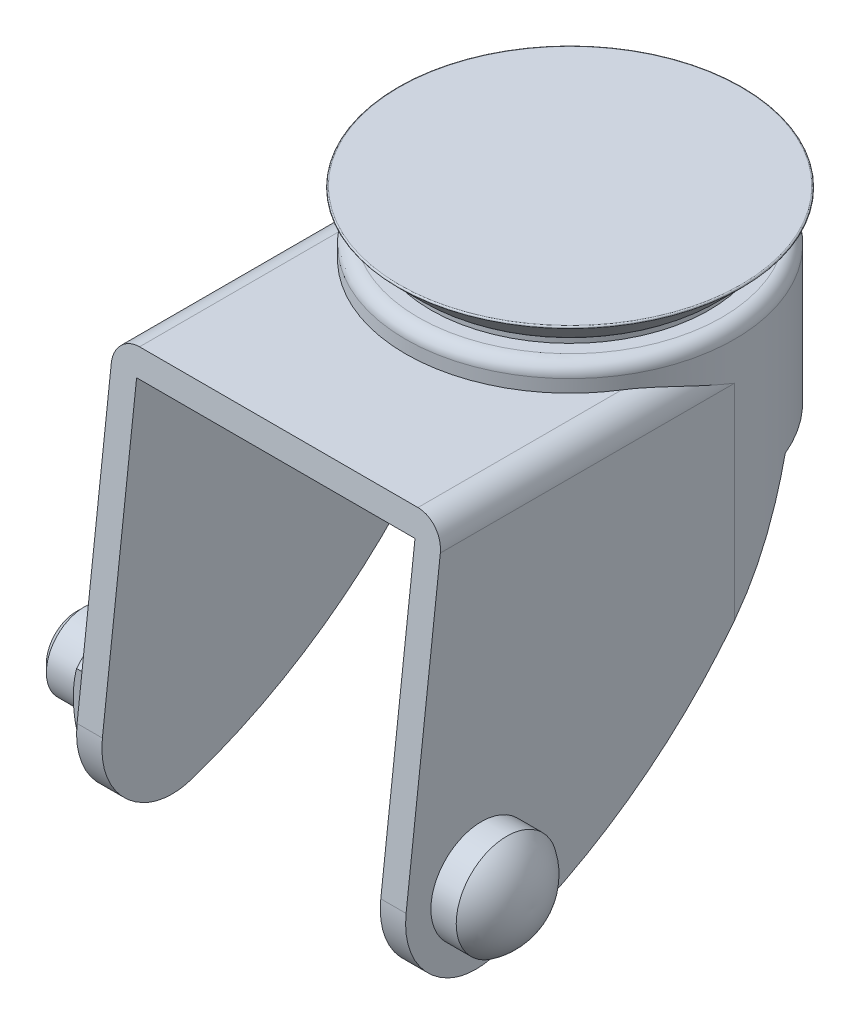
SolidWorks part; units mm, degrees
material "A6061"
ref_plane "前视基准面" through (0, 0, 0) normal (0, 0, 1) x (1, 0, 0)
ref_plane "上视基准面" through (0, 0, 0) normal (0, 1, 0) x (1, 0, 0)
ref_plane "右视基准面" through (0, 0, 0) normal (1, 0, 0) x (0, 0, -1)
sketch "草图1" plane through (0, 0, 0) normal (0, 0, 1) x (1, 0, 0)
  line L0 (0, 0) -> (11, 0)
  line L1 (11, 0) -> (11, -3)
  line L2 (11, -3) -> (12, -3)
  line L3 (13, -4) -> (13, -51)
  line L4 (13, -51) -> (0, -51)
  line L5 (0, -51) -> (0, 0)
  line L6 (0, -51) -> (0, 0) construction
  arc A0 (12, -3) -> (13, -4) centre (12, -4) cw
revolve "旋转1" add sketch "草图1" angle 360 about L6 reverse direction yes
ref_plane "基准面1" through (0, 0, 0) normal (0, 0, 1) x (1, 0, 0)
ref_plane "基准面2" through (0, 0, 0) normal (0, 0, 1) x (1, 0, 0)
sketch "草图2" plane through (0, 0, 0) normal (0, 0, 1) x (1, 0, 0)
  line L0 (-13, -7) -> (-13, -56)
  line L1 (-13, -56) -> (13, -56)
  line L2 (13, -56) -> (13, -7)
  line L3 (11, -5) -> (-11, -5)
  arc A0 (13, -7) -> (11, -5) centre (11, -7) ccw
  arc A1 (-11, -5) -> (-13, -7) centre (-11, -7) ccw
extrude "凸台-拉伸1" add sketch "草图2" along normal blind 60
sketch "草图3" plane through (0, 0, 0) normal (0, 0, 1) x (1, 0, 0)
  line L0 (-11, -58) -> (11, -58)
  line L1 (11, -58) -> (11, -7)
  line L2 (11, -7) -> (-11, -7)
  line L3 (-11, -7) -> (-11, -58)
extrude "切除-拉伸1" cut sketch "草图3" along normal blind 70
ref_plane "基准面3" through (0, -4, 0) normal (0, 1, 0) x (1, 0, 0)
sketch "草图4" plane through (0, -4, 0) normal (0, 1, 0) x (1, 0, 0)
  circle A0 centre (0, 0) radius 11
extrude "切除-拉伸2" cut sketch "草图4" against normal blind 51
sketch "草图5" plane through (0, 0, 0) normal (1, 0, 0) x (0, 0, -1)
  line L0 (-150, -300) -> (150, -300)
  line L1 (150, -300) -> (150, -14.8)
  line L2 (150, -14.8) -> (5, -14.8)
  line L3 (-25.96, -30.3084) -> (-23, -4.8)
  line L4 (-23, -4.8) -> (-150, -4.8)
  line L5 (-150, -4.8) -> (-150, -300)
  arc A0 (5, -14.8) -> (-18.8511, -36.6319) centre (-31.629, 1.2723) cw
  arc A1 (-18.8511, -36.6319) -> (-22.69, -36.3632) centre (-20.4483, -31.8939) cw
  arc A2 (-22.69, -36.3632) -> (-25.96, -30.3084) centre (-20, -31) cw
extrude "切除-拉伸3" cut sketch "草图5" along normal blind 200 and the other way blind 200
ref_plane "基准面4" through (0, 0, 20) normal (0, 0, 1) x (1, 0, 0)
sketch "草图6" plane through (0, 0, 20) normal (0, 0, 1) x (1, 0, 0)
  line L0 (13, -31) -> (13, -27)
  line L1 (13, -27) -> (15, -27)
  line L2 (17, -31) -> (13, -31)
  line L3 (17, -31) -> (13, -31) construction
  arc A0 (15, -27) -> (17, -31) centre (12.5072, -30.7464) cw
revolve "旋转2" add sketch "草图6" angle 360 about L3 reverse direction yes
sketch "草图7" plane through (0, 0, 20) normal (0, 0, 1) x (1, 0, 0)
  line L0 (-19, -31) -> (-19, -28.6135)
  line L1 (-19, -28.6135) -> (-18.3865, -28)
  line L2 (-18.3865, -28) -> (-16, -28)
  line L3 (-16, -28) -> (-16, -28.6)
  line L4 (-15, -26.2) -> (-13, -26.2)
  line L5 (-13, -26.2) -> (-13, -31)
  line L6 (-13, -31) -> (-19, -31)
  line L7 (-13, -31) -> (-19, -31) construction
  arc A0 (-16, -28.6) -> (-15, -26.2) centre (-10.0931, -29.6529) cw
revolve "旋转3" add sketch "草图7" angle 360 about L7 reverse direction yes
cosmetic thread "装饰螺纹线1" parameters "D1"=1.9, "D2"=4.773
ref_plane "基准面5" through (-13, 0, 0) normal (1, 0, 0) x (0, 0, -1)
sketch "草图8" plane through (-13, 0, 0) normal (1, 0, 0) x (0, 0, -1)
  line L0 (-23.6, -33.0785) -> (-20, -35.1569)
  line L1 (-20, -35.1569) -> (-16.4, -33.0785)
  line L2 (-16.4, -33.0785) -> (-16.4, -28.9215)
  line L3 (-16.4, -28.9215) -> (-20, -26.8431)
  line L4 (-20, -26.8431) -> (-23.6, -28.9215)
  line L5 (-23.6, -28.9215) -> (-23.6, -33.0785)
  circle A0 centre (-20, -31) radius 5.3
extrude "切除-拉伸4" cut sketch "草图8" against normal blind 200
sketch "草图9" plane through (0, 0, 0) normal (0, 0, 1) x (1, 0, 0)
  line L0 (0, 0) -> (13.5086, 0)
  line L1 (13.5793, -0.1707) -> (11.5429, -2.2071)
  line L2 (10.8358, -2.5) -> (0, -2.5)
  line L3 (0, -2.5) -> (0, 0)
  line L4 (0, -2.5) -> (0, 0) construction
  arc A0 (13.5086, 0) -> (13.5793, -0.1707) centre (13.5086, -0.1) cw
  arc A1 (11.5429, -2.2071) -> (10.8358, -2.5) centre (10.8358, -1.5) cw
revolve "旋转4" add sketch "草图9" angle 360 about L4 reverse direction yes
ref_plane "body_to_plate XY" through (0, 0, 0) normal (0, 1, 0) x (1, 0, 0)
ref_plane "body_to_plate XZ" through (0, 0, 0) normal (0, 0, 1) x (1, 0, 0)
ref_plane "body_to_plate YZ" through (0, 0, 0) normal (1, 0, 0) x (0, 0, -1)
ref_axis "body_to_plate X" through (-80.9, 0, 0) along (1, 0, 0)
ref_axis "body_to_plate Y" through (0, 0, 50) along (0, 0, -1)
ref_axis "body_to_plate Z" through (0, 50, 0) along (0, -1, 0)
sketch3d "body_to_plate"
  point P0 (0, 0, 0)
ref_plane "body_to_wheel XY" through (0, 0, 0) normal (1, 0, 0) x (0, 0, -1)
ref_plane "body_to_wheel XZ" through (0, -31, 0) normal (0, -1, 0) x (-1, 0, 0)
ref_plane "body_to_wheel YZ" through (0, 0, 20) normal (0, 0, -1) x (-1, 0, 0)
ref_axis "body_to_wheel X" through (0, -31, 80.9) along (0, 0, -1)
ref_axis "body_to_wheel Y" through (0, -50, 20) along (0, 1, 0)
ref_axis "body_to_wheel Z" through (80.9, -31, 20) along (-1, 0, 0)
sketch3d "body_to_wheel"
  point P0 (0, -31, 20)
